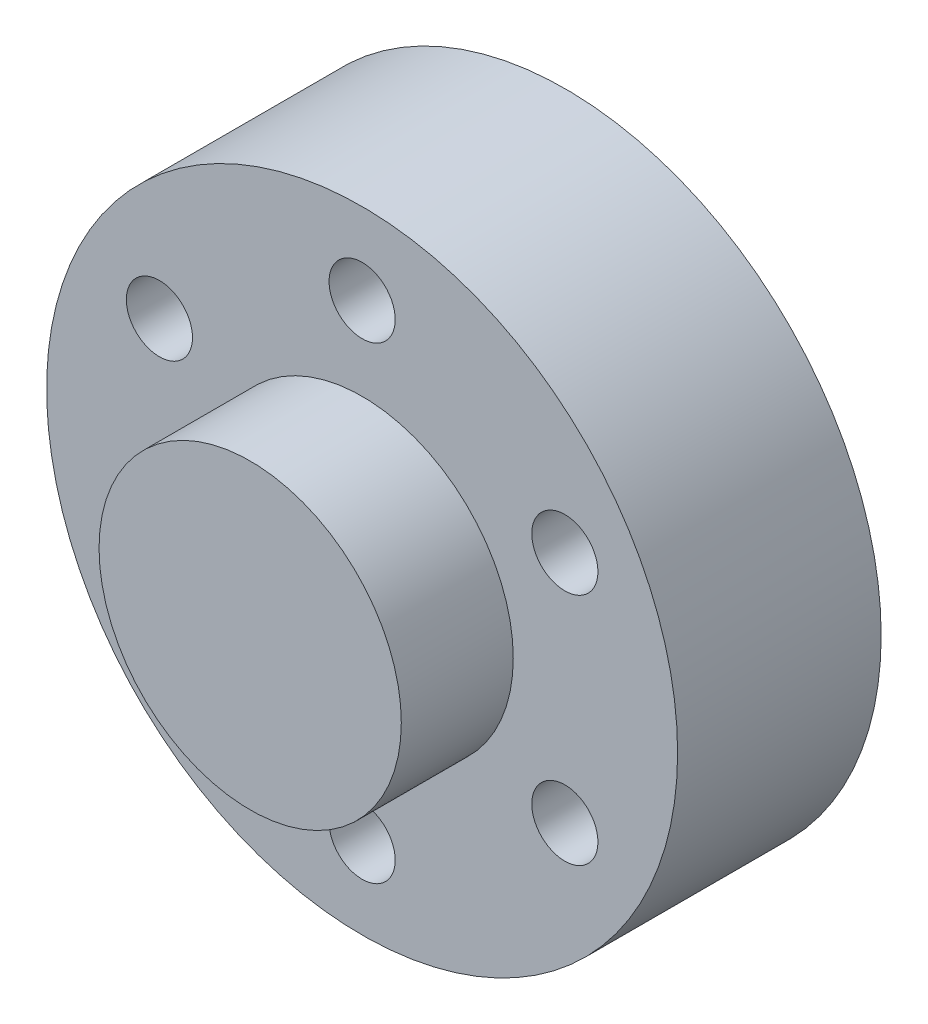
SolidWorks part; units mm, degrees
ref_plane "Front Plane" through (0, 0, 0) normal (0, 0, 1) x (1, 0, 0)
ref_plane "Top Plane" through (0, 0, 0) normal (0, 1, 0) x (1, 0, 0)
ref_plane "Right Plane" through (0, 0, 0) normal (1, 0, 0) x (0, 0, -1)
sketch "Sketch2" plane through (0, 0, 0) normal (0, 0, 1) x (1, 0, 0)
  line L0 (0, 20.3178) -> (0, -21.083) construction
  circle A0 centre (0, 0) radius 9.5
  circle A1 centre (0, 0) radius 11.5 construction
  circle A3 centre (0, 0) radius 15.5
  circle A4 centre (0, 11.5) radius 1.625
  circle A10 centre (9.9593, 5.75) radius 1.625
  circle A11 centre (9.9593, -5.75) radius 1.625
  circle A12 centre (0, -11.5) radius 1.625
  circle A13 centre (-9.9593, -5.75) radius 1.625
  circle A14 centre (-9.9593, 5.75) radius 1.625
  point P21 (1.7321, -1)
  point P22 (0.866, -0.5)
  point P23 (0, 0)
  dimension "D1" = 19
  dimension "D2" = 6
  dimension "D3" = 23
  dimension "D4" = 31
  dimension "D5" = 3.25
extrude "Boss-Extrude1" add sketch "Sketch2" along normal blind 10 contours A3 A14 A13 A12 A11 A10 A4 A0 | A0 region at (0, 0, 0) region at (-15.0616, 0, 0)
sketch "Sketch3" plane through (0, 0, 10) normal (0, 0, 1) x (1, 0, 0)
  circle A0 centre (0, 0) radius 7.425
  dimension "D1" = 14.85
extrude "Boss-Extrude2" add sketch "Sketch3" along normal blind 5.5
sketch "Sketch6" plane through (0, 0, 0) normal (0, 0, -1) x (-1, 0, 0)
  circle A0 centre (0, 0) radius 7.425
  dimension "D1" = 14.85
extrude "Boss-Extrude4" add sketch "Sketch6" along normal blind 5.5 contours A0
sketch "Sketch7" plane through (0, 0, -5.5) normal (0, 0, -1) x (-1, 0, 0)
  circle A0 centre (0, 0) radius 2
  dimension "D1" = 4
extrude "Boss-Extrude5" add sketch "Sketch7" along normal blind 1
fillet "Fillet2" radius 0.05 1 edges at (-2, 0, -6.5)
sketch "Sketch9" plane through (0, 0, -6.5) normal (0, 0, -1) x (-1, 0, 0)
  line L1 (-1.2247, 1.25) -> (1.2247, 1.25)
  arc A0 (-1.2247, 1.25) -> (1.2247, 1.25) centre (0, 0) ccw
  circle A1 centre (0, -0.25) radius 1.5 construction
  dimension "D1" = 3.5
  dimension "D2" = 3
extrude "Cut-Extrude1" cut sketch "Sketch9" against normal blind 11
